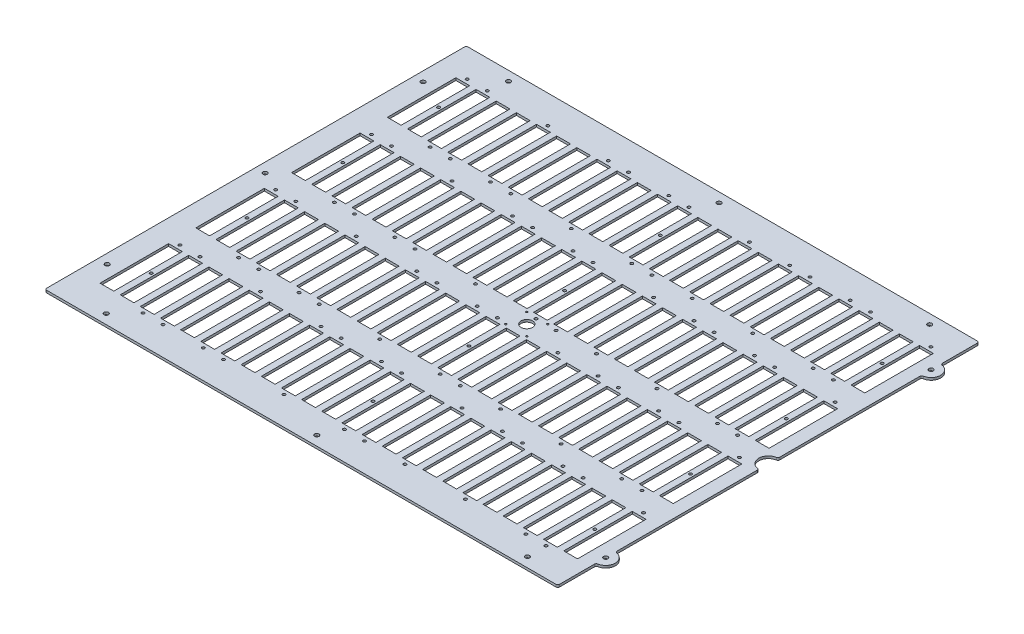
SolidWorks part; units mm, degrees
ref_plane "Front Plane" through (0, 0, 0) normal (0, 0, 1) x (1, 0, 0)
ref_plane "Top Plane" through (0, 0, 0) normal (0, 1, 0) x (1, 0, 0)
ref_plane "Right Plane" through (0, 0, 0) normal (1, 0, 0) x (0, 0, -1)
sketch "Sketch1" plane through (0, 0, 0) normal (0, 1, 0) x (1, 0, 0)
  line L0 (340.2584, 228.6) -> (340.2584, 279.5524)
  line L1 (-340.2584, -279.5524) -> (340.2584, -279.5524)
  line L2 (-340.2584, -279.5524) -> (-340.2584, 279.5524)
  line L3 (-340.2584, 279.5524) -> (340.2584, 279.5524)
  line L4 (340.2584, -279.5524) -> (340.2584, -228.6)
  line L5 (-340.2584, -279.5524) -> (340.2584, 279.5524) construction
  line L6 (-340.2584, 279.5524) -> (340.2584, -279.5524) construction
  line L7 (340.2584, 12.7) -> (340.2584, 203.2)
  line L8 (340.2584, -203.2) -> (340.2584, -12.7)
  arc A0 (340.2584, 203.2) -> (340.2584, 228.6) centre (340.2584, 215.9) ccw
  arc A1 (340.2584, -228.6) -> (340.2584, -203.2) centre (340.2584, -215.9) ccw
  arc A2 (340.2584, 12.7) -> (340.2584, -12.7) centre (340.2584, 0) ccw
  point P0 (0, 0)
  dimension "D3" = 25.4
  dimension "D4" = 63.6524
  dimension "D5" = 215.9
  dimension "D6" = 215.9
  dimension "D1" = 559.1048
  dimension "D2" = 680.5168
extrude "Boss-Extrude1" add sketch "Sketch1" along normal blind 3.175
sketch "Sketch17" plane through (0, 3.175, 0) normal (0, 1, 0) x (1, 0, 0)
  line L0 (340.2584, 279.5524) -> (-340.2584, 279.5524) construction
  line L1 (-314.8584, 254.1524) -> (327.5584, 254.1524) construction
  line L2 (-314.8584, 254.1524) -> (-314.8584, -254.1524) construction
  line L3 (-314.8584, -254.1524) -> (327.5584, -254.1524) construction
  line L4 (327.5584, 254.1524) -> (327.5584, -254.1524) construction
  line L5 (-340.2584, 279.5524) -> (-340.2584, -279.5524) construction
  line L6 (-340.2584, -279.5524) -> (340.2584, -279.5524) construction
  line L7 (340.2584, -203.2) -> (340.2584, -12.7) construction
  line L8 (-283.8406, 236.1184) -> (-265.5526, 236.1184)
  line L9 (-310.5912, 236.1184) -> (-292.3032, 236.1184)
  line L10 (-310.5912, 236.1184) -> (-310.5912, 145.1864)
  line L11 (-310.5912, 145.1864) -> (-292.3032, 145.1864)
  line L12 (-292.3032, 236.1184) -> (-292.3032, 145.1864)
  line L13 (-283.8406, 236.1184) -> (-283.8406, 145.1864)
  line L14 (-265.5526, 236.1184) -> (-265.5526, 145.1864)
  line L15 (-283.8406, 145.1864) -> (-265.5526, 145.1864)
  line L16 (-257.09, 236.1184) -> (-238.802, 236.1184)
  line L17 (-257.09, 236.1184) -> (-257.09, 145.1864)
  line L18 (-238.802, 236.1184) -> (-238.802, 145.1864)
  line L19 (-257.09, 145.1864) -> (-238.802, 145.1864)
  line L20 (-230.3393, 236.1184) -> (-212.0513, 236.1184)
  line L21 (-230.3393, 236.1184) -> (-230.3393, 145.1864)
  line L22 (-212.0513, 236.1184) -> (-212.0513, 145.1864)
  line L23 (-230.3393, 145.1864) -> (-212.0513, 145.1864)
  line L24 (-203.5887, 236.1184) -> (-185.3007, 236.1184)
  line L25 (-203.5887, 236.1184) -> (-203.5887, 145.1864)
  line L26 (-185.3007, 236.1184) -> (-185.3007, 145.1864)
  line L27 (-203.5887, 145.1864) -> (-185.3007, 145.1864)
  line L28 (-176.8381, 236.1184) -> (-158.5501, 236.1184)
  line L29 (-176.8381, 236.1184) -> (-176.8381, 145.1864)
  line L30 (-158.5501, 236.1184) -> (-158.5501, 145.1864)
  line L31 (-176.8381, 145.1864) -> (-158.5501, 145.1864)
  line L32 (-150.0875, 236.1184) -> (-131.7995, 236.1184)
  line L33 (-150.0875, 236.1184) -> (-150.0875, 145.1864)
  line L34 (-131.7995, 236.1184) -> (-131.7995, 145.1864)
  line L35 (-150.0875, 145.1864) -> (-131.7995, 145.1864)
  line L36 (-123.3369, 236.1184) -> (-105.0489, 236.1184)
  line L37 (-123.3369, 236.1184) -> (-123.3369, 145.1864)
  line L38 (-105.0489, 236.1184) -> (-105.0489, 145.1864)
  line L39 (-123.3369, 145.1864) -> (-105.0489, 145.1864)
  line L40 (-96.5863, 236.1184) -> (-78.2983, 236.1184)
  line L41 (-96.5863, 236.1184) -> (-96.5863, 145.1864)
  line L42 (-78.2983, 236.1184) -> (-78.2983, 145.1864)
  line L43 (-96.5863, 145.1864) -> (-78.2983, 145.1864)
  line L44 (-69.8356, 236.1184) -> (-51.5476, 236.1184)
  line L45 (-69.8356, 236.1184) -> (-69.8356, 145.1864)
  line L46 (-51.5476, 236.1184) -> (-51.5476, 145.1864)
  line L47 (-69.8356, 145.1864) -> (-51.5476, 145.1864)
  line L48 (-43.085, 236.1184) -> (-24.797, 236.1184)
  line L49 (-43.085, 236.1184) -> (-43.085, 145.1864)
  line L50 (-24.797, 236.1184) -> (-24.797, 145.1864)
  line L51 (-43.085, 145.1864) -> (-24.797, 145.1864)
  line L52 (-16.3344, 236.1184) -> (1.9536, 236.1184)
  line L53 (-16.3344, 236.1184) -> (-16.3344, 145.1864)
  line L54 (1.9536, 236.1184) -> (1.9536, 145.1864)
  line L55 (-16.3344, 145.1864) -> (1.9536, 145.1864)
  line L56 (10.4162, 236.1184) -> (28.7042, 236.1184)
  line L57 (10.4162, 236.1184) -> (10.4162, 145.1864)
  line L58 (28.7042, 236.1184) -> (28.7042, 145.1864)
  line L59 (10.4162, 145.1864) -> (28.7042, 145.1864)
  line L60 (37.1668, 236.1184) -> (55.4548, 236.1184)
  line L61 (37.1668, 236.1184) -> (37.1668, 145.1864)
  line L62 (55.4548, 236.1184) -> (55.4548, 145.1864)
  line L63 (37.1668, 145.1864) -> (55.4548, 145.1864)
  line L64 (63.9174, 236.1184) -> (82.2054, 236.1184)
  line L65 (63.9174, 236.1184) -> (63.9174, 145.1864)
  line L66 (82.2054, 236.1184) -> (82.2054, 145.1864)
  line L67 (63.9174, 145.1864) -> (82.2054, 145.1864)
  line L68 (90.6681, 236.1184) -> (108.9561, 236.1184)
  line L69 (90.6681, 236.1184) -> (90.6681, 145.1864)
  line L70 (108.9561, 236.1184) -> (108.9561, 145.1864)
  line L71 (90.6681, 145.1864) -> (108.9561, 145.1864)
  line L72 (117.4187, 236.1184) -> (135.7067, 236.1184)
  line L73 (117.4187, 236.1184) -> (117.4187, 145.1864)
  line L74 (135.7067, 236.1184) -> (135.7067, 145.1864)
  line L75 (117.4187, 145.1864) -> (135.7067, 145.1864)
  line L76 (144.1693, 236.1184) -> (162.4573, 236.1184)
  line L77 (144.1693, 236.1184) -> (144.1693, 145.1864)
  line L78 (162.4573, 236.1184) -> (162.4573, 145.1864)
  line L79 (144.1693, 145.1864) -> (162.4573, 145.1864)
  line L80 (170.9199, 236.1184) -> (189.2079, 236.1184)
  line L81 (170.9199, 236.1184) -> (170.9199, 145.1864)
  line L82 (189.2079, 236.1184) -> (189.2079, 145.1864)
  line L83 (170.9199, 145.1864) -> (189.2079, 145.1864)
  line L84 (197.6705, 236.1184) -> (215.9585, 236.1184)
  line L85 (197.6705, 236.1184) -> (197.6705, 145.1864)
  line L86 (215.9585, 236.1184) -> (215.9585, 145.1864)
  line L87 (197.6705, 145.1864) -> (215.9585, 145.1864)
  line L88 (224.4211, 236.1184) -> (242.7091, 236.1184)
  line L89 (224.4211, 236.1184) -> (224.4211, 145.1864)
  line L90 (242.7091, 236.1184) -> (242.7091, 145.1864)
  line L91 (224.4211, 145.1864) -> (242.7091, 145.1864)
  line L92 (251.1718, 236.1184) -> (269.4598, 236.1184)
  line L93 (251.1718, 236.1184) -> (251.1718, 145.1864)
  line L94 (269.4598, 236.1184) -> (269.4598, 145.1864)
  line L95 (251.1718, 145.1864) -> (269.4598, 145.1864)
  line L96 (277.9224, 236.1184) -> (296.2104, 236.1184)
  line L97 (277.9224, 236.1184) -> (277.9224, 145.1864)
  line L98 (296.2104, 236.1184) -> (296.2104, 145.1864)
  line L99 (277.9224, 145.1864) -> (296.2104, 145.1864)
  line L100 (304.673, 236.1184) -> (322.961, 236.1184)
  line L101 (304.673, 236.1184) -> (304.673, 145.1864)
  line L102 (322.961, 236.1184) -> (322.961, 145.1864)
  line L103 (304.673, 145.1864) -> (322.961, 145.1864)
  line L104 (-283.8406, 109.0422) -> (-265.5526, 109.0422)
  line L105 (-283.8406, 109.0422) -> (-283.8406, 18.1102)
  line L106 (-265.5526, 109.0422) -> (-265.5526, 18.1102)
  line L107 (-283.8406, 18.1102) -> (-265.5526, 18.1102)
  line L108 (-257.09, 109.0422) -> (-238.802, 109.0422)
  line L109 (-257.09, 109.0422) -> (-257.09, 18.1102)
  line L110 (-238.802, 109.0422) -> (-238.802, 18.1102)
  line L111 (-257.09, 18.1102) -> (-238.802, 18.1102)
  line L112 (-230.3393, 109.0422) -> (-212.0513, 109.0422)
  line L113 (-230.3393, 109.0422) -> (-230.3393, 18.1102)
  line L114 (-212.0513, 109.0422) -> (-212.0513, 18.1102)
  line L115 (-230.3393, 18.1102) -> (-212.0513, 18.1102)
  line L116 (-203.5887, 109.0422) -> (-185.3007, 109.0422)
  line L117 (-203.5887, 109.0422) -> (-203.5887, 18.1102)
  line L118 (-185.3007, 109.0422) -> (-185.3007, 18.1102)
  line L119 (-203.5887, 18.1102) -> (-185.3007, 18.1102)
  line L120 (-176.8381, 109.0422) -> (-158.5501, 109.0422)
  line L121 (-176.8381, 109.0422) -> (-176.8381, 18.1102)
  line L122 (-158.5501, 109.0422) -> (-158.5501, 18.1102)
  line L123 (-176.8381, 18.1102) -> (-158.5501, 18.1102)
  line L124 (-150.0875, 109.0422) -> (-131.7995, 109.0422)
  line L125 (-150.0875, 109.0422) -> (-150.0875, 18.1102)
  line L126 (-131.7995, 109.0422) -> (-131.7995, 18.1102)
  line L127 (-150.0875, 18.1102) -> (-131.7995, 18.1102)
  line L128 (-123.3369, 109.0422) -> (-105.0489, 109.0422)
  line L129 (-123.3369, 109.0422) -> (-123.3369, 18.1102)
  line L130 (-105.0489, 109.0422) -> (-105.0489, 18.1102)
  line L131 (-123.3369, 18.1102) -> (-105.0489, 18.1102)
  line L132 (-96.5863, 109.0422) -> (-78.2983, 109.0422)
  line L133 (-96.5863, 109.0422) -> (-96.5863, 18.1102)
  line L134 (-78.2983, 109.0422) -> (-78.2983, 18.1102)
  line L135 (-96.5863, 18.1102) -> (-78.2983, 18.1102)
  line L136 (-69.8356, 109.0422) -> (-51.5476, 109.0422)
  line L137 (-69.8356, 109.0422) -> (-69.8356, 18.1102)
  line L138 (-51.5476, 109.0422) -> (-51.5476, 18.1102)
  line L139 (-69.8356, 18.1102) -> (-51.5476, 18.1102)
  line L140 (-43.085, 109.0422) -> (-24.797, 109.0422)
  line L141 (-43.085, 109.0422) -> (-43.085, 18.1102)
  line L142 (-24.797, 109.0422) -> (-24.797, 18.1102)
  line L143 (-43.085, 18.1102) -> (-24.797, 18.1102)
  line L144 (-16.3344, 109.0422) -> (1.9536, 109.0422)
  line L145 (-16.3344, 109.0422) -> (-16.3344, 18.1102)
  line L146 (1.9536, 109.0422) -> (1.9536, 18.1102)
  line L147 (-16.3344, 18.1102) -> (1.9536, 18.1102)
  line L148 (10.4162, 109.0422) -> (28.7042, 109.0422)
  line L149 (10.4162, 109.0422) -> (10.4162, 18.1102)
  line L150 (28.7042, 109.0422) -> (28.7042, 18.1102)
  line L151 (10.4162, 18.1102) -> (28.7042, 18.1102)
  line L152 (37.1668, 109.0422) -> (55.4548, 109.0422)
  line L153 (37.1668, 109.0422) -> (37.1668, 18.1102)
  line L154 (55.4548, 109.0422) -> (55.4548, 18.1102)
  line L155 (37.1668, 18.1102) -> (55.4548, 18.1102)
  line L156 (63.9174, 109.0422) -> (82.2054, 109.0422)
  line L157 (63.9174, 109.0422) -> (63.9174, 18.1102)
  line L158 (82.2054, 109.0422) -> (82.2054, 18.1102)
  line L159 (63.9174, 18.1102) -> (82.2054, 18.1102)
  line L160 (90.6681, 109.0422) -> (108.9561, 109.0422)
  line L161 (90.6681, 109.0422) -> (90.6681, 18.1102)
  line L162 (108.9561, 109.0422) -> (108.9561, 18.1102)
  line L163 (90.6681, 18.1102) -> (108.9561, 18.1102)
  line L164 (117.4187, 109.0422) -> (135.7067, 109.0422)
  line L165 (117.4187, 109.0422) -> (117.4187, 18.1102)
  line L166 (135.7067, 109.0422) -> (135.7067, 18.1102)
  line L167 (117.4187, 18.1102) -> (135.7067, 18.1102)
  line L168 (144.1693, 109.0422) -> (162.4573, 109.0422)
  line L169 (144.1693, 109.0422) -> (144.1693, 18.1102)
  line L170 (162.4573, 109.0422) -> (162.4573, 18.1102)
  line L171 (144.1693, 18.1102) -> (162.4573, 18.1102)
  line L172 (170.9199, 109.0422) -> (189.2079, 109.0422)
  line L173 (170.9199, 109.0422) -> (170.9199, 18.1102)
  line L174 (189.2079, 109.0422) -> (189.2079, 18.1102)
  line L175 (170.9199, 18.1102) -> (189.2079, 18.1102)
  line L176 (197.6705, 109.0422) -> (215.9585, 109.0422)
  line L177 (197.6705, 109.0422) -> (197.6705, 18.1102)
  line L178 (215.9585, 109.0422) -> (215.9585, 18.1102)
  line L179 (197.6705, 18.1102) -> (215.9585, 18.1102)
  line L180 (224.4211, 109.0422) -> (242.7091, 109.0422)
  line L181 (224.4211, 109.0422) -> (224.4211, 18.1102)
  line L182 (242.7091, 109.0422) -> (242.7091, 18.1102)
  line L183 (224.4211, 18.1102) -> (242.7091, 18.1102)
  line L184 (251.1718, 109.0422) -> (269.4598, 109.0422)
  line L185 (251.1718, 109.0422) -> (251.1718, 18.1102)
  line L186 (269.4598, 109.0422) -> (269.4598, 18.1102)
  line L187 (251.1718, 18.1102) -> (269.4598, 18.1102)
  line L188 (277.9224, 109.0422) -> (296.2104, 109.0422)
  line L189 (277.9224, 109.0422) -> (277.9224, 18.1102)
  line L190 (296.2104, 109.0422) -> (296.2104, 18.1102)
  line L191 (277.9224, 18.1102) -> (296.2104, 18.1102)
  line L192 (304.673, 109.0422) -> (322.961, 109.0422)
  line L193 (304.673, 109.0422) -> (304.673, 18.1102)
  line L194 (322.961, 109.0422) -> (322.961, 18.1102)
  line L195 (304.673, 18.1102) -> (322.961, 18.1102)
  line L196 (-283.8406, -18.034) -> (-265.5526, -18.034)
  line L197 (-283.8406, -18.034) -> (-283.8406, -108.966)
  line L198 (-265.5526, -18.034) -> (-265.5526, -108.966)
  line L199 (-283.8406, -108.966) -> (-265.5526, -108.966)
  line L200 (-257.09, -18.034) -> (-238.802, -18.034)
  line L201 (-257.09, -18.034) -> (-257.09, -108.966)
  line L202 (-238.802, -18.034) -> (-238.802, -108.966)
  line L203 (-257.09, -108.966) -> (-238.802, -108.966)
  line L204 (-230.3393, -18.034) -> (-212.0513, -18.034)
  line L205 (-230.3393, -18.034) -> (-230.3393, -108.966)
  line L206 (-212.0513, -18.034) -> (-212.0513, -108.966)
  line L207 (-230.3393, -108.966) -> (-212.0513, -108.966)
  line L208 (-203.5887, -18.034) -> (-185.3007, -18.034)
  line L209 (-203.5887, -18.034) -> (-203.5887, -108.966)
  line L210 (-185.3007, -18.034) -> (-185.3007, -108.966)
  line L211 (-203.5887, -108.966) -> (-185.3007, -108.966)
  line L212 (-176.8381, -18.034) -> (-158.5501, -18.034)
  line L213 (-176.8381, -18.034) -> (-176.8381, -108.966)
  line L214 (-158.5501, -18.034) -> (-158.5501, -108.966)
  line L215 (-176.8381, -108.966) -> (-158.5501, -108.966)
  line L216 (-150.0875, -18.034) -> (-131.7995, -18.034)
  line L217 (-150.0875, -18.034) -> (-150.0875, -108.966)
  line L218 (-131.7995, -18.034) -> (-131.7995, -108.966)
  line L219 (-150.0875, -108.966) -> (-131.7995, -108.966)
  line L220 (-123.3369, -18.034) -> (-105.0489, -18.034)
  line L221 (-123.3369, -18.034) -> (-123.3369, -108.966)
  line L222 (-105.0489, -18.034) -> (-105.0489, -108.966)
  line L223 (-123.3369, -108.966) -> (-105.0489, -108.966)
  line L224 (-96.5863, -18.034) -> (-78.2983, -18.034)
  line L225 (-96.5863, -18.034) -> (-96.5863, -108.966)
  line L226 (-78.2983, -18.034) -> (-78.2983, -108.966)
  line L227 (-96.5863, -108.966) -> (-78.2983, -108.966)
  line L228 (-69.8356, -18.034) -> (-51.5476, -18.034)
  line L229 (-69.8356, -18.034) -> (-69.8356, -108.966)
  line L230 (-51.5476, -18.034) -> (-51.5476, -108.966)
  line L231 (-69.8356, -108.966) -> (-51.5476, -108.966)
  line L232 (-43.085, -18.034) -> (-24.797, -18.034)
  line L233 (-43.085, -18.034) -> (-43.085, -108.966)
  line L234 (-24.797, -18.034) -> (-24.797, -108.966)
  line L235 (-43.085, -108.966) -> (-24.797, -108.966)
  line L236 (-16.3344, -18.034) -> (1.9536, -18.034)
  line L237 (-16.3344, -18.034) -> (-16.3344, -108.966)
  line L238 (1.9536, -18.034) -> (1.9536, -108.966)
  line L239 (-16.3344, -108.966) -> (1.9536, -108.966)
  line L240 (10.4162, -18.034) -> (28.7042, -18.034)
  line L241 (10.4162, -18.034) -> (10.4162, -108.966)
  line L242 (28.7042, -18.034) -> (28.7042, -108.966)
  line L243 (10.4162, -108.966) -> (28.7042, -108.966)
  line L244 (37.1668, -18.034) -> (55.4548, -18.034)
  line L245 (37.1668, -18.034) -> (37.1668, -108.966)
  line L246 (55.4548, -18.034) -> (55.4548, -108.966)
  line L247 (37.1668, -108.966) -> (55.4548, -108.966)
  line L248 (63.9174, -18.034) -> (82.2054, -18.034)
  line L249 (63.9174, -18.034) -> (63.9174, -108.966)
  line L250 (82.2054, -18.034) -> (82.2054, -108.966)
  line L251 (63.9174, -108.966) -> (82.2054, -108.966)
  line L252 (90.6681, -18.034) -> (108.9561, -18.034)
  line L253 (90.6681, -18.034) -> (90.6681, -108.966)
  line L254 (108.9561, -18.034) -> (108.9561, -108.966)
  line L255 (90.6681, -108.966) -> (108.9561, -108.966)
  line L256 (117.4187, -18.034) -> (135.7067, -18.034)
  line L257 (117.4187, -18.034) -> (117.4187, -108.966)
  line L258 (135.7067, -18.034) -> (135.7067, -108.966)
  line L259 (117.4187, -108.966) -> (135.7067, -108.966)
  line L260 (144.1693, -18.034) -> (162.4573, -18.034)
  line L261 (144.1693, -18.034) -> (144.1693, -108.966)
  line L262 (162.4573, -18.034) -> (162.4573, -108.966)
  line L263 (144.1693, -108.966) -> (162.4573, -108.966)
  line L264 (170.9199, -18.034) -> (189.2079, -18.034)
  line L265 (170.9199, -18.034) -> (170.9199, -108.966)
  line L266 (189.2079, -18.034) -> (189.2079, -108.966)
  line L267 (170.9199, -108.966) -> (189.2079, -108.966)
  line L268 (197.6705, -18.034) -> (215.9585, -18.034)
  line L269 (197.6705, -18.034) -> (197.6705, -108.966)
  line L270 (215.9585, -18.034) -> (215.9585, -108.966)
  line L271 (197.6705, -108.966) -> (215.9585, -108.966)
  line L272 (224.4211, -18.034) -> (242.7091, -18.034)
  line L273 (224.4211, -18.034) -> (224.4211, -108.966)
  line L274 (242.7091, -18.034) -> (242.7091, -108.966)
  line L275 (224.4211, -108.966) -> (242.7091, -108.966)
  line L276 (251.1718, -18.034) -> (269.4598, -18.034)
  line L277 (251.1718, -18.034) -> (251.1718, -108.966)
  line L278 (269.4598, -18.034) -> (269.4598, -108.966)
  line L279 (251.1718, -108.966) -> (269.4598, -108.966)
  line L280 (277.9224, -18.034) -> (296.2104, -18.034)
  line L281 (277.9224, -18.034) -> (277.9224, -108.966)
  line L282 (296.2104, -18.034) -> (296.2104, -108.966)
  line L283 (277.9224, -108.966) -> (296.2104, -108.966)
  line L284 (304.673, -18.034) -> (322.961, -18.034)
  line L285 (304.673, -18.034) -> (304.673, -108.966)
  line L286 (322.961, -18.034) -> (322.961, -108.966)
  line L287 (304.673, -108.966) -> (322.961, -108.966)
  line L288 (-283.8406, -145.1102) -> (-265.5526, -145.1102)
  line L289 (-283.8406, -145.1102) -> (-283.8406, -236.0422)
  line L290 (-265.5526, -145.1102) -> (-265.5526, -236.0422)
  line L291 (-283.8406, -236.0422) -> (-265.5526, -236.0422)
  line L292 (-257.09, -145.1102) -> (-238.802, -145.1102)
  line L293 (-257.09, -145.1102) -> (-257.09, -236.0422)
  line L294 (-238.802, -145.1102) -> (-238.802, -236.0422)
  line L295 (-257.09, -236.0422) -> (-238.802, -236.0422)
  line L296 (-230.3393, -145.1102) -> (-212.0513, -145.1102)
  line L297 (-230.3393, -145.1102) -> (-230.3393, -236.0422)
  line L298 (-212.0513, -145.1102) -> (-212.0513, -236.0422)
  line L299 (-230.3393, -236.0422) -> (-212.0513, -236.0422)
  line L300 (-203.5887, -145.1102) -> (-185.3007, -145.1102)
  line L301 (-203.5887, -145.1102) -> (-203.5887, -236.0422)
  line L302 (-185.3007, -145.1102) -> (-185.3007, -236.0422)
  line L303 (-203.5887, -236.0422) -> (-185.3007, -236.0422)
  line L304 (-176.8381, -145.1102) -> (-158.5501, -145.1102)
  line L305 (-176.8381, -145.1102) -> (-176.8381, -236.0422)
  line L306 (-158.5501, -145.1102) -> (-158.5501, -236.0422)
  line L307 (-176.8381, -236.0422) -> (-158.5501, -236.0422)
  line L308 (-150.0875, -145.1102) -> (-131.7995, -145.1102)
  line L309 (-150.0875, -145.1102) -> (-150.0875, -236.0422)
  line L310 (-131.7995, -145.1102) -> (-131.7995, -236.0422)
  line L311 (-150.0875, -236.0422) -> (-131.7995, -236.0422)
  line L312 (-123.3369, -145.1102) -> (-105.0489, -145.1102)
  line L313 (-123.3369, -145.1102) -> (-123.3369, -236.0422)
  line L314 (-105.0489, -145.1102) -> (-105.0489, -236.0422)
  line L315 (-123.3369, -236.0422) -> (-105.0489, -236.0422)
  line L316 (-96.5863, -145.1102) -> (-78.2983, -145.1102)
  line L317 (-96.5863, -145.1102) -> (-96.5863, -236.0422)
  line L318 (-78.2983, -145.1102) -> (-78.2983, -236.0422)
  line L319 (-96.5863, -236.0422) -> (-78.2983, -236.0422)
  line L320 (-69.8356, -145.1102) -> (-51.5476, -145.1102)
  line L321 (-69.8356, -145.1102) -> (-69.8356, -236.0422)
  line L322 (-51.5476, -145.1102) -> (-51.5476, -236.0422)
  line L323 (-69.8356, -236.0422) -> (-51.5476, -236.0422)
  line L324 (-43.085, -145.1102) -> (-24.797, -145.1102)
  line L325 (-43.085, -145.1102) -> (-43.085, -236.0422)
  line L326 (-24.797, -145.1102) -> (-24.797, -236.0422)
  line L327 (-43.085, -236.0422) -> (-24.797, -236.0422)
  line L328 (-16.3344, -145.1102) -> (1.9536, -145.1102)
  line L329 (-16.3344, -145.1102) -> (-16.3344, -236.0422)
  line L330 (1.9536, -145.1102) -> (1.9536, -236.0422)
  line L331 (-16.3344, -236.0422) -> (1.9536, -236.0422)
  line L332 (10.4162, -145.1102) -> (28.7042, -145.1102)
  line L333 (10.4162, -145.1102) -> (10.4162, -236.0422)
  line L334 (28.7042, -145.1102) -> (28.7042, -236.0422)
  line L335 (10.4162, -236.0422) -> (28.7042, -236.0422)
  line L336 (37.1668, -145.1102) -> (55.4548, -145.1102)
  line L337 (37.1668, -145.1102) -> (37.1668, -236.0422)
  line L338 (55.4548, -145.1102) -> (55.4548, -236.0422)
  line L339 (37.1668, -236.0422) -> (55.4548, -236.0422)
  line L340 (63.9174, -145.1102) -> (82.2054, -145.1102)
  line L341 (63.9174, -145.1102) -> (63.9174, -236.0422)
  line L342 (82.2054, -145.1102) -> (82.2054, -236.0422)
  line L343 (63.9174, -236.0422) -> (82.2054, -236.0422)
  line L344 (90.6681, -145.1102) -> (108.9561, -145.1102)
  line L345 (90.6681, -145.1102) -> (90.6681, -236.0422)
  line L346 (108.9561, -145.1102) -> (108.9561, -236.0422)
  line L347 (90.6681, -236.0422) -> (108.9561, -236.0422)
  line L348 (117.4187, -145.1102) -> (135.7067, -145.1102)
  line L349 (117.4187, -145.1102) -> (117.4187, -236.0422)
  line L350 (135.7067, -145.1102) -> (135.7067, -236.0422)
  line L351 (117.4187, -236.0422) -> (135.7067, -236.0422)
  line L352 (144.1693, -145.1102) -> (162.4573, -145.1102)
  line L353 (144.1693, -145.1102) -> (144.1693, -236.0422)
  line L354 (162.4573, -145.1102) -> (162.4573, -236.0422)
  line L355 (144.1693, -236.0422) -> (162.4573, -236.0422)
  line L356 (170.9199, -145.1102) -> (189.2079, -145.1102)
  line L357 (170.9199, -145.1102) -> (170.9199, -236.0422)
  line L358 (189.2079, -145.1102) -> (189.2079, -236.0422)
  line L359 (170.9199, -236.0422) -> (189.2079, -236.0422)
  line L360 (197.6705, -145.1102) -> (215.9585, -145.1102)
  line L361 (197.6705, -145.1102) -> (197.6705, -236.0422)
  line L362 (215.9585, -145.1102) -> (215.9585, -236.0422)
  line L363 (197.6705, -236.0422) -> (215.9585, -236.0422)
  line L364 (224.4211, -145.1102) -> (242.7091, -145.1102)
  line L365 (224.4211, -145.1102) -> (224.4211, -236.0422)
  line L366 (242.7091, -145.1102) -> (242.7091, -236.0422)
  line L367 (224.4211, -236.0422) -> (242.7091, -236.0422)
  line L368 (251.1718, -145.1102) -> (269.4598, -145.1102)
  line L369 (251.1718, -145.1102) -> (251.1718, -236.0422)
  line L370 (269.4598, -145.1102) -> (269.4598, -236.0422)
  line L371 (251.1718, -236.0422) -> (269.4598, -236.0422)
  line L372 (277.9224, -145.1102) -> (296.2104, -145.1102)
  line L373 (277.9224, -145.1102) -> (277.9224, -236.0422)
  line L374 (296.2104, -145.1102) -> (296.2104, -236.0422)
  line L375 (277.9224, -236.0422) -> (296.2104, -236.0422)
  line L376 (304.673, -145.1102) -> (322.961, -145.1102)
  line L377 (304.673, -145.1102) -> (304.673, -236.0422)
  line L378 (322.961, -145.1102) -> (322.961, -236.0422)
  line L379 (304.673, -236.0422) -> (322.961, -236.0422)
  line L380 (-310.5912, 109.0422) -> (-292.3032, 109.0422)
  line L381 (-310.5912, 109.0422) -> (-310.5912, 18.1102)
  line L382 (-292.3032, 109.0422) -> (-292.3032, 18.1102)
  line L383 (-310.5912, 18.1102) -> (-292.3032, 18.1102)
  line L384 (-310.5912, -18.034) -> (-292.3032, -18.034)
  line L385 (-310.5912, -18.034) -> (-310.5912, -108.966)
  line L386 (-292.3032, -18.034) -> (-292.3032, -108.966)
  line L387 (-310.5912, -108.966) -> (-292.3032, -108.966)
  line L388 (-310.5912, -145.1102) -> (-292.3032, -145.1102)
  line L389 (-310.5912, -145.1102) -> (-310.5912, -236.0422)
  line L390 (-292.3032, -145.1102) -> (-292.3032, -236.0422)
  line L391 (-310.5912, -236.0422) -> (-292.3032, -236.0422)
  line L392 (340.2584, -279.5524) -> (340.2584, -228.6) construction
  dimension "D1" = 25.4
  dimension "D2" = 25.4
  dimension "D3" = 25.4
  dimension "D4" = 12.7
  dimension "D5" = 18.288
  dimension "D6" = 90.932
  dimension "D7" = 4.2672
  dimension "D8" = 18.034
  dimension "D9" = 508.3048
  dimension "D10" = 642.4168
  dimension "D11" = 24
  dimension "D13" = 17.2974
  dimension "D14" = 43.5102
  dimension "D12" = 4
extrude "Cut-Extrude5" cut sketch "Sketch17" against normal through all
hole_wizard "#25 (0.1495) Diameter Hole1" positions "Sketch18" profile "Sketch19" hole size "#25" standard "ANSI Inch" end condition through all
sketch "Sketch18" plane through (0, 3.175, 0) normal (0, 1, 0) x (1, 0, 0)
  line L10 (-340.2584, 241.9604) -> (340.2584, 241.9604) construction
  line L11 (-340.2584, 279.5524) -> (-340.2584, -279.5524) construction
  line L12 (340.2584, 228.6) -> (340.2584, 279.5524) construction
  line L15 (-292.3032, 236.1184) -> (-310.5912, 236.1184) construction
  line L16 (-340.2584, 139.3444) -> (340.2584, 139.3444) construction
  line L17 (340.2584, 12.7) -> (340.2584, 203.2) construction
  line L19 (-310.5912, 145.1864) -> (-292.3032, 145.1864) construction
  line L23 (-301.4472, 139.3444) -> (-301.4472, 241.9604) construction
  line L24 (-274.6966, 139.3444) -> (-274.6966, 241.9604) construction
  line L25 (-247.946, 139.3444) -> (-247.946, 241.9604) construction
  line L26 (-221.1953, 139.3444) -> (-221.1953, 241.9604) construction
  line L27 (-194.4447, 139.3444) -> (-194.4447, 241.9604) construction
  line L28 (-167.6941, 139.3444) -> (-167.6941, 241.9604) construction
  line L29 (-140.9435, 139.3444) -> (-140.9435, 241.9604) construction
  line L30 (-114.1929, 139.3444) -> (-114.1929, 241.9604) construction
  line L31 (-87.4423, 139.3444) -> (-87.4423, 241.9604) construction
  line L32 (-60.6916, 139.3444) -> (-60.6916, 241.9604) construction
  line L33 (-33.941, 139.3444) -> (-33.941, 241.9604) construction
  line L34 (-7.1904, 139.3444) -> (-7.1904, 241.9604) construction
  line L35 (19.5602, 139.3444) -> (19.5602, 241.9604) construction
  line L36 (46.3108, 139.3444) -> (46.3108, 241.9604) construction
  line L37 (73.0614, 139.3444) -> (73.0614, 241.9604) construction
  line L38 (99.8121, 139.3444) -> (99.8121, 241.9604) construction
  line L39 (126.5627, 139.3444) -> (126.5627, 241.9604) construction
  line L40 (153.3133, 139.3444) -> (153.3133, 241.9604) construction
  line L41 (180.0639, 139.3444) -> (180.0639, 241.9604) construction
  line L42 (206.8145, 139.3444) -> (206.8145, 241.9604) construction
  line L43 (233.5651, 139.3444) -> (233.5651, 241.9604) construction
  line L44 (260.3158, 139.3444) -> (260.3158, 241.9604) construction
  line L45 (287.0664, 139.3444) -> (287.0664, 241.9604) construction
  line L46 (313.817, 139.3444) -> (313.817, 241.9604) construction
  point P259 (-301.4472, 241.9604)
  point P269 (-274.6966, 241.9604)
  point P270 (-247.946, 139.3444)
  point P272 (-221.1953, 139.3444)
  point P275 (-194.4447, 241.9604)
  point P276 (-167.6941, 139.3444)
  point P278 (-140.9435, 139.3444)
  point P281 (-114.1929, 241.9604)
  point P283 (-87.4423, 241.9604)
  point P284 (-60.6916, 139.3444)
  point P287 (-33.941, 241.9604)
  point P289 (-7.1904, 241.9604)
  point P290 (19.5602, 139.3444)
  point P292 (46.3108, 139.3444)
  point P295 (73.0614, 241.9604)
  point P296 (99.8121, 139.3444)
  point P299 (126.5627, 241.9604)
  point P301 (153.3133, 241.9604)
  point P302 (180.0639, 139.3444)
  point P305 (206.8145, 241.9604)
  point P307 (233.5651, 241.9604)
  point P308 (260.3158, 139.3444)
  point P310 (287.0664, 139.3444)
  point P313 (313.817, 241.9604)
  point P365 (-301.4472, 114.8842)
  point P366 (-274.6966, 114.8842)
  point P367 (-247.946, 12.2682)
  point P368 (-221.1953, 12.2682)
  point P369 (-194.4447, 114.8842)
  point P370 (-167.6941, 12.2682)
  point P371 (-140.9435, 12.2682)
  point P372 (-114.1929, 114.8842)
  point P373 (-87.4423, 114.8842)
  point P374 (-60.6916, 12.2682)
  point P375 (-33.941, 114.8842)
  point P376 (-7.1904, 114.8842)
  point P377 (19.5602, 12.2682)
  point P378 (46.3108, 12.2682)
  point P379 (73.0614, 114.8842)
  point P380 (99.8121, 12.2682)
  point P381 (126.5627, 114.8842)
  point P382 (153.3133, 114.8842)
  point P383 (180.0639, 12.2682)
  point P384 (206.8145, 114.8842)
  point P385 (233.5651, 114.8842)
  point P386 (260.3158, 12.2682)
  point P387 (287.0664, 12.2682)
  point P388 (313.817, 114.8842)
  point P389 (-301.4472, -12.192)
  point P390 (-274.6966, -12.192)
  point P391 (-247.946, -114.808)
  point P392 (-221.1953, -114.808)
  point P393 (-194.4447, -12.192)
  point P394 (-167.6941, -114.808)
  point P395 (-140.9435, -114.808)
  point P396 (-114.1929, -12.192)
  point P397 (-87.4423, -12.192)
  point P398 (-60.6916, -114.808)
  point P399 (-33.941, -12.192)
  point P400 (-7.1904, -12.192)
  point P401 (19.5602, -114.808)
  point P402 (46.3108, -114.808)
  point P403 (73.0614, -12.192)
  point P404 (99.8121, -114.808)
  point P405 (126.5627, -12.192)
  point P406 (153.3133, -12.192)
  point P407 (180.0639, -114.808)
  point P408 (206.8145, -12.192)
  point P409 (233.5651, -12.192)
  point P410 (260.3158, -114.808)
  point P411 (287.0664, -114.808)
  point P412 (313.817, -12.192)
  point P413 (-301.4472, -139.2682)
  point P414 (-274.6966, -139.2682)
  point P415 (-247.946, -241.8842)
  point P416 (-221.1953, -241.8842)
  point P417 (-194.4447, -139.2682)
  point P418 (-167.6941, -241.8842)
  point P419 (-140.9435, -241.8842)
  point P420 (-114.1929, -139.2682)
  point P421 (-87.4423, -139.2682)
  point P422 (-60.6916, -241.8842)
  point P423 (-33.941, -139.2682)
  point P424 (-7.1904, -139.2682)
  point P425 (19.5602, -241.8842)
  point P426 (46.3108, -241.8842)
  point P427 (73.0614, -139.2682)
  point P428 (99.8121, -241.8842)
  point P429 (126.5627, -139.2682)
  point P430 (153.3133, -139.2682)
  point P431 (180.0639, -241.8842)
  point P432 (206.8145, -139.2682)
  point P433 (233.5651, -139.2682)
  point P434 (260.3158, -241.8842)
  point P435 (287.0664, -241.8842)
  point P436 (313.817, -139.2682)
  dimension "D1" = 5.842
  dimension "D2" = 5.842
sketch "Sketch19" plane through (313.817, 3.175, 139.2682) normal (1, 0, 0) x (0, 0, 1)
  line L0 (0, 0) -> (0, 3.175)
  line L1 (0, 3.175) -> (1.8986, 3.175)
  line L2 (1.8986, 3.175) -> (1.8986, 0)
  line L5 (1.8986, 0) -> (0, 0)
  line L11 (0, -6.35) -> (0, 107.95) construction
  dimension "Thru Hole Dia." = 3.7973
  dimension "Thru Hole Depth" = 3.175
fillet "Fillet1" radius 2.54 10 edges at (-340.2584, 1.5875, -279.5524) (-340.2584, 1.5875, 279.5524) (340.2584, 1.5875, 279.5524) (340.2584, 1.5875, 228.6) (340.2584, 1.5875, 203.2) (340.2584, 1.5875, 12.7) (340.2584, 1.5875, -12.7) (340.2584, 1.5875, -203.2) (340.2584, 1.5875, -279.5524) (340.2584, 1.5875, -228.6)
hole_wizard "#6 Clearance Hole1" positions "Sketch8" profile "Sketch9" hole size "#6" standard "ANSI Inch" end condition through all
sketch "Sketch8" plane through (0, 3.175, 0) normal (0, 1, 0) x (1, 0, 0)
  line L13 (-292.3032, 236.1184) -> (-283.8406, 145.1864) construction
  line L15 (1.9536, 236.1184) -> (10.4162, 145.1864) construction
  line L17 (296.2104, 236.1184) -> (304.673, 145.1864) construction
  line L18 (-292.3032, 109.0422) -> (-283.8406, 18.1102) construction
  line L19 (1.9536, 109.0422) -> (10.4162, 18.1102) construction
  line L20 (296.2104, 109.0422) -> (304.673, 18.1102) construction
  line L21 (-292.3032, -18.034) -> (-283.8406, -108.966) construction
  line L22 (1.9536, -18.034) -> (10.4162, -108.966) construction
  line L23 (296.2104, -18.034) -> (304.673, -108.966) construction
  line L24 (-292.3032, -145.1102) -> (-283.8406, -236.0422) construction
  line L25 (1.9536, -145.1102) -> (10.4162, -236.0422) construction
  line L26 (296.2104, -145.1102) -> (304.673, -236.0422) construction
  point P129 (-288.0719, 190.6524)
  point P131 (6.1849, 190.6524)
  point P133 (300.4417, 190.6524)
  point P146 (-288.0719, 63.5762)
  point P147 (6.1849, 63.5762)
  point P148 (300.4417, 63.5762)
  point P155 (-288.0719, -63.5)
  point P156 (6.1849, -63.5)
  point P157 (300.4417, -63.5)
  point P164 (-288.0719, -190.5762)
  point P165 (6.1849, -190.5762)
  point P166 (300.4417, -190.5762)
  dimension "D1" = 4
sketch "Sketch9" plane through (300.4417, 3.175, 190.5762) normal (1, 0, 0) x (0, 0, 1)
  line L0 (0, 0) -> (0, 3.175)
  line L1 (0, 3.175) -> (1.8986, 3.175)
  line L2 (1.8986, 3.175) -> (1.8986, 0)
  line L5 (1.8986, 0) -> (0, 0)
  line L11 (0, -6.35) -> (0, 107.95) construction
  dimension "Thru Hole Dia." = 3.7973
  dimension "Thru Hole Depth" = 3.175
hole_wizard "#2 Clearance Hole1" positions "Sketch13" profile "Sketch14" hole size "#2" standard "ANSI Inch" end condition through all
sketch "Sketch13" plane through (0, 3.175, 0) normal (0, 1, 0) x (1, 0, 0)
  line L9 (322.961, -108.966) -> (322.961, -18.034) construction
  line L10 (322.961, -18.034) -> (304.673, -18.034) construction
  line L18 (10.4162, 18.1102) -> (28.7042, -18.034) construction
  line L21 (5.6261, -13.9319) -> (33.5661, -13.9319) construction
  line L22 (5.6261, -13.9319) -> (5.6261, 14.0081) construction
  line L23 (5.6261, 14.0081) -> (33.5661, 14.0081) construction
  line L24 (33.5661, -13.9319) -> (33.5661, 14.0081) construction
  line L25 (5.6261, -13.9319) -> (33.5661, 14.0081) construction
  line L26 (5.6261, 14.0081) -> (33.5661, -13.9319) construction
  line L27 (10.4162, 18.1102) -> (28.7042, 18.1102) construction
  point P129 (5.6261, 14.0081)
  point P132 (5.6261, -13.9319)
  point P135 (33.5661, -13.9319)
  point P138 (33.5661, 14.0081)
  dimension "D1" = 27.94
  dimension "D2" = 27.94
  dimension "D3" = 4.1021
sketch "Sketch14" plane through (33.5661, 3.175, -14.0081) normal (1, 0, 0) x (0, 0, 1)
  line L0 (0, 0) -> (0, 3.175)
  line L1 (0, 3.175) -> (1.2192, 3.175)
  line L2 (1.2192, 3.175) -> (1.2192, 0)
  line L5 (1.2192, 0) -> (0, 0)
  line L11 (0, -6.35) -> (0, 107.95) construction
  dimension "Thru Hole Dia." = 2.4384
  dimension "Thru Hole Depth" = 3.175
sketch "Sketch20" plane through (0, 3.175, 0) normal (0, 1, 0) x (1, 0, 0)
  line L0 (5.6261, 14.0081) -> (33.5661, -13.9319) construction
  circle A0 centre (19.5961, 0.0381) radius 7.62
  dimension "D1" = 15.24
extrude "Cut-Extrude6" cut sketch "Sketch20" against normal through all
hole_wizard "#1 (0.228) Diameter Hole1" positions "Sketch21" profile "Sketch22" hole size "#1" standard "ANSI Inch" end condition through all
sketch "Sketch21" plane through (0, 3.175, 0) normal (0, 1, 0) x (1, 0, 0)
  point P0 (287.274, -266.8524)
  point P3 (340.2584, -215.9)
  point P6 (340.2584, 0)
  point P9 (340.2584, 215.9)
  point P12 (287.274, 266.8524)
  point P15 (7.874, 266.8524)
  point P18 (-271.526, 266.8524)
  point P21 (-327.5584, 209.55)
  point P24 (-327.5584, 0)
  point P27 (-327.5584, -209.55)
  point P30 (-271.526, -266.8524)
  point P33 (7.874, -266.8524)
sketch "Sketch22" plane through (287.274, 3.175, 266.8524) normal (1, 0, 0) x (0, 0, 1)
  line L0 (0, 0) -> (0, 3.175)
  line L1 (0, 3.175) -> (2.8956, 3.175)
  line L2 (2.8956, 3.175) -> (2.8956, 0)
  line L5 (2.8956, 0) -> (0, 0)
  line L11 (0, -6.35) -> (0, 107.95) construction
  dimension "Thru Hole Dia." = 5.7912
  dimension "Thru Hole Depth" = 3.175
